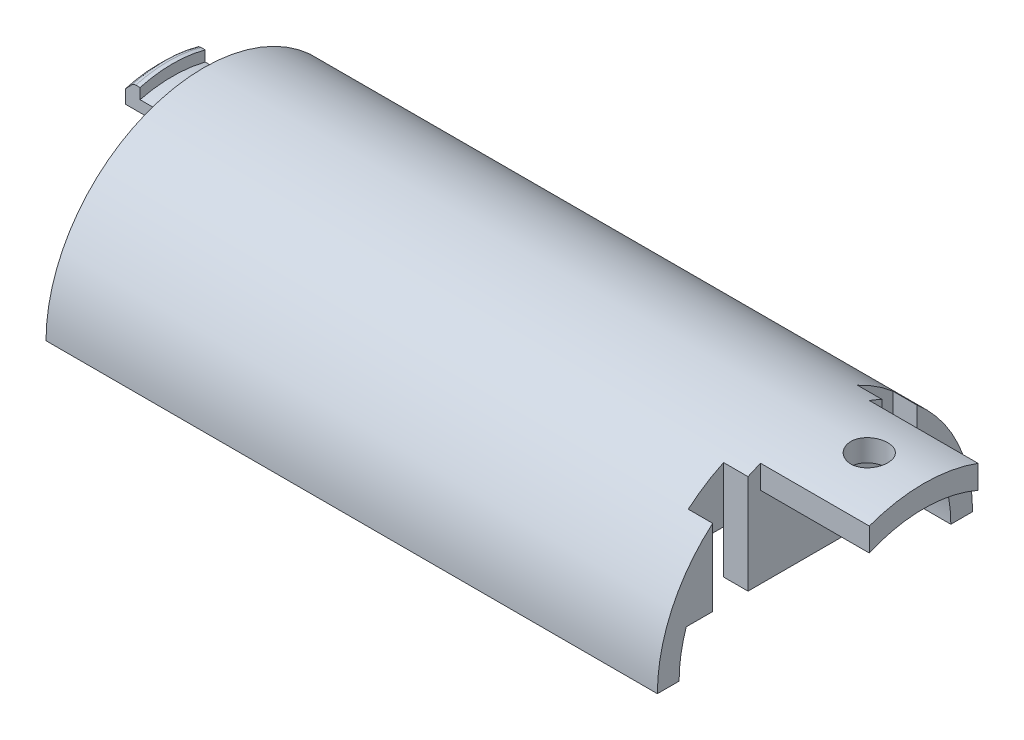
SolidWorks part; units mm, degrees
ref_plane "Alzado" through (0, 0, 0) normal (1, 0, 0) x (0, 1, 0)
ref_plane "Planta" through (0, 0, 0) normal (0, 0, 1) x (0, 1, 0)
ref_plane "Vista lateral" through (0, 0, 0) normal (0, 1, 0) x (-1, 0, 0)
sketch "Croquis2" plane through (0, 0, 0) normal (1, 0, 0) x (0, 1, 0)
  line L0 (0, -14.5) -> (0, 14.5)
  arc A1 (0, -14.5) -> (0, 14.5) centre (0, 0) ccw
  arc A2 (0, -12.5) -> (0, 12.5) centre (0, 0) ccw
  dimension "D1" = 25
  dimension "D2" = 2
extrude "Saliente-Extruir1" add sketch "Croquis2" along normal mid plane 61.75 contours A2 L0 A1 region at (0, 0.3242, -13.5)
ref_plane "Plano1" through (-21.625, 0, 0) normal (1, 0, 0) x (0, 0, -1)
ref_plane "Plano2" through (23.125, 0, 0) normal (1, 0, 0) x (0, 0, -1)
sketch "Croquis3" plane through (-21.625, 0, 0) normal (1, 0, 0) x (0, 0, -1)
  line L0 (-12.5, 0) -> (-3.75, 0)
  line L1 (3.75, 0) -> (12.5, 0)
  arc A0 (12.5, 0) -> (-12.5, 0) centre (0, 0) ccw construction
  arc A1 (12.5, 0) -> (-12.5, 0) centre (0, 0) ccw
  arc A2 (3.75, 0) -> (-3.75, 0) centre (0, 0) ccw
  dimension "D1" = 7.5
extrude "Saliente-Extruir2" add sketch "Croquis3" against normal blind 2
sketch "Croquis4" plane through (23.125, 0, 0) normal (1, 0, 0) x (0, 0, -1)
  line L0 (-11.8427, 4) -> (11.8427, 4)
  line L1 (-9.6047, 8) -> (9.6047, 8)
  line L2 (-4.325, 4) -> (-4.325, -8)
  line L3 (-4.325, -8) -> (4.325, -8)
  line L4 (4.325, -8) -> (4.325, 4)
  line L5 (0, 0) -> (0, 4) construction
  line L6 (4.325, -6) -> (-4.325, -6)
  line L8 (14.5, 0) -> (12.5, 0) construction
  arc A0 (12.5, 0) -> (-12.5, 0) centre (0, 0) ccw construction
  arc A1 (11.8427, 4) -> (-11.8427, 4) centre (0, 0) ccw
  circle A2 centre (0, 0) radius 3
  point P7 (0, 12.5)
  dimension "D4" = 6
  dimension "D1" = 4.5
  dimension "D2" = 8.5
  dimension "D3" = 8.65
  dimension "D5" = 8
  dimension "D6" = 2
extrude "Saliente-Extruir3" add sketch "Croquis4" against normal blind 20 contours L1 A1 region at (23.125, 9.831, 0)
extrude "Saliente-Extruir4" add sketch "Croquis4<4>" along normal blind 3 contours L1 A1 | L0 A1 L1 region at (23.125, 5.9321, 0) region at (23.125, 9.831, 0)
sketch "Croquis4<4>" plane through (23.125, 0, 0) normal (1, 0, 0) x (0, 0, -1) same geometry as "Croquis4"
ref_plane "Plano4" through (0, 13.5, 0) normal (0, 1, 0) x (-1, 0, 0)
sketch "Croquis6" plane through (0, 13.5, 0) normal (0, 1, 0) x (-1, 0, 0)
  line L0 (30.875, -14.5) -> (30.875, 14.5) construction
  line L1 (30.875, -14.5) -> (30.875, 14.5) construction
  line L2 (28.875, -3) -> (30.875, -3)
  line L3 (28.875, -3) -> (28.875, 3)
  line L4 (30.875, -3) -> (30.875, 3)
  line L5 (28.875, 3) -> (30.875, 3)
  line L6 (28.875, -3) -> (30.875, 3) construction
  line L7 (30.875, -3) -> (28.875, 3) construction
  point P3 (29.875, 0)
  point P11 (30.875, 0)
  dimension "D1" = 6
  dimension "D2" = 2
extrude "Saliente-Extruir6" add sketch "Croquis6" against normal blind 2.5
sketch "Croquis7" plane through (-30.875, 0, 0) normal (-1, 0, 0) x (0, -1, 0)
  line L0 (-11, -3) -> (-11, 3) construction
  line L1 (-11, -3) -> (-11, 3) construction
  line L3 (-11, 3) -> (-12.0334, 3)
  line L4 (-11, 3) -> (-11, -3)
  line L5 (-11, -3) -> (-12.0334, -3)
  arc A0 (-12.0334, 3) -> (-12.0334, -3) centre (0, 0) ccw
  arc A1 (-11, 3) -> (-11, -3) centre (0, 0) ccw
  point P2 (-12.4018, 0)
  point P3 (-11.4018, 0)
  line M9 (-12.1347, -3) -> (-11, -3)
  line M10 (-11, -3) -> (-11, 3)
  line M11 (-11, 3) -> (-12.1347, 3)
  dimension "D1" = 1
extrude "Cortar-Extruir1" cut sketch "Croquis7" against normal up to next contours A1 M10 region at (-30.875, 11.1609, 0)
extrude "Saliente-Extruir7" add sketch "Croquis7<4>" along normal blind 4.2 contours A1 A0 M11 M9 region at (-30.875, 11.7731, 0)
sketch "Croquis7<4>" plane through (-30.875, 0, 0) normal (-1, 0, 0) x (0, -1, 0) same geometry as "Croquis7"
sketch "Croquis8" plane through (-35.075, 0, 0) normal (-1, 0, 0) x (0, -1, 0)
  line L0 (-11, 3) -> (-13, 3)
  line L1 (-13.4018, 0) -> (-11.4018, 0) construction
  line L4 (-13, -3) -> (-11, -3)
  arc A0 (-13, -3) -> (-13, 3) centre (-2, 0) cw
  arc A3 (-11, 3) -> (-11, -3) centre (0, 0) ccw construction
  arc A4 (-11, 3) -> (-11, -3) centre (0, 0) ccw
  point P2 (-13.4018, 0)
  point P9 (-11.4018, 0)
  dimension "D1" = 2
  dimension "D2" = 2
extrude "Saliente-Extruir9" add sketch "Croquis8" against normal blind 1.35
chamfer "Chaflán3" distance 0.75 angle 45 1 edges at (-35.075, 13.4018, 0)
fillet "Redondeo1" radius 0.5 1 edges at (-34.325, 13.4018, 0)
chamfer "Chaflán4" distance 1 angle 45 1 edges at (-28.875, 12.5, 0)
sketch "Croquis9" plane through (30.875, 0, 0) normal (1, 0, 0) x (0, 1, 0)
  line L1 (4, 11.8427) -> (4, -11.8427)
  line L2 (0, -12.5) -> (0, -14.5)
  line L3 (0, 14.5) -> (0, 12.5)
  line L4 (0, -12.5) -> (0, -14.5)
  line L5 (0, 14.5) -> (0, 12.5)
  line L6 (4, 11.8427) -> (4, -11.8427)
  arc A1 (4, -11.8427) -> (4, 11.8427) centre (0, 0) ccw
  arc A2 (0, -12.5) -> (0, 12.5) centre (0, 0) ccw
  arc A3 (0, -14.5) -> (0, 14.5) centre (0, 0) ccw
  arc A4 (0, -12.5) -> (0, 12.5) centre (0, 0) ccw
  arc A5 (0, -14.5) -> (0, 14.5) centre (0, 0) ccw
  arc A6 (4, -11.8427) -> (4, 11.8427) centre (0, 0) ccw
  arc M5 (0, 12.5) -> (0, -12.5) centre (0, 0) cw
  line M6 (0, -12.5) -> (0, -14.5)
  arc M7 (0, -14.5) -> (0, 14.5) centre (0, 0) ccw
  line M8 (0, 14.5) -> (0, 12.5)
  dimension "D1" = 0
  dimension "D2" = 0
extrude "Cortar-Extruir2" cut sketch "Croquis9" against normal blind 5.5 contours L6 M5 | M8 M5 M6 M7 region at (30.875, 7.5239, 0) region at (30.875, 2.0794, 12.6545)
sketch "Croquis10" plane through (25.375, 0, 0) normal (1, 0, 0) x (0, 1, 0)
  line L0 (11.4564, 5) -> (13.6107, 5)
  line L1 (11.4564, -5) -> (13.6107, -5)
  line L2 (14.5, 0) -> (12.5, 0) construction
  arc A0 (0, -12.5) -> (0, 12.5) centre (0, 0) ccw construction
  arc A1 (11.4564, -5) -> (11.4564, 5) centre (0, 0) ccw
  arc A4 (0, -14.5) -> (0, 14.5) centre (0, 0) ccw construction
  arc A5 (13.6107, -5) -> (13.6107, 5) centre (0, 0) ccw
  dimension "D1" = 5
extrude "Saliente-Extruir10" add sketch "Croquis10" along normal blind 10
ref_plane "Plano5" through (0, 14.5, 0) normal (0, 1, 0) x (-1, 0, 0)
sketch "Croquis11" plane through (0, 14.5, 0) normal (0, 1, 0) x (-1, 0, 0)
  line L0 (-35.375, 5) -> (-25.375, -5) construction
  circle A0 centre (-30.375, 0) radius 1.7
  point P4 (-30.375, 0)
  point P7 (0, 0)
  point P8 (0, 0)
  point P10 (0, 0)
  dimension "D1" = 3.4
extrude "Cortar-Extruir3" cut sketch "Croquis11" against normal up to next
sketch "Croquis14" plane through (0, 4, 0) normal (0, -1, 0) x (1, 0, 0)
  line L0 (25.375, 11.8427) -> (25.375, -11.8427) construction
  line L1 (25.375, 9.41) -> (23.125, 9.41)
  line L2 (25.375, 9.41) -> (25.375, 6.16)
  line L3 (25.375, 6.16) -> (23.125, 6.16)
  line L4 (23.125, 9.41) -> (23.125, 6.16)
  line L5 (23.125, 11.8427) -> (23.125, -11.8427) construction
  line L6 (0, 0) -> (10.089, 0) construction
  line L7 (25.375, -9.41) -> (23.125, -9.41)
  line L8 (25.375, -9.41) -> (25.375, -6.16)
  line L9 (25.375, -6.16) -> (23.125, -6.16)
  line L10 (23.125, -9.41) -> (23.125, -6.16)
  point P15 (25.375, 7.785)
  point P16 (25.375, -7.785)
  dimension "D1" = 15.57
  dimension "D2" = 3.25
extrude "Cortar-Extruir6" cut sketch "Croquis14" against normal through all
equation "\"D2@Croquis8\"=\"D1@Croquis8\""
